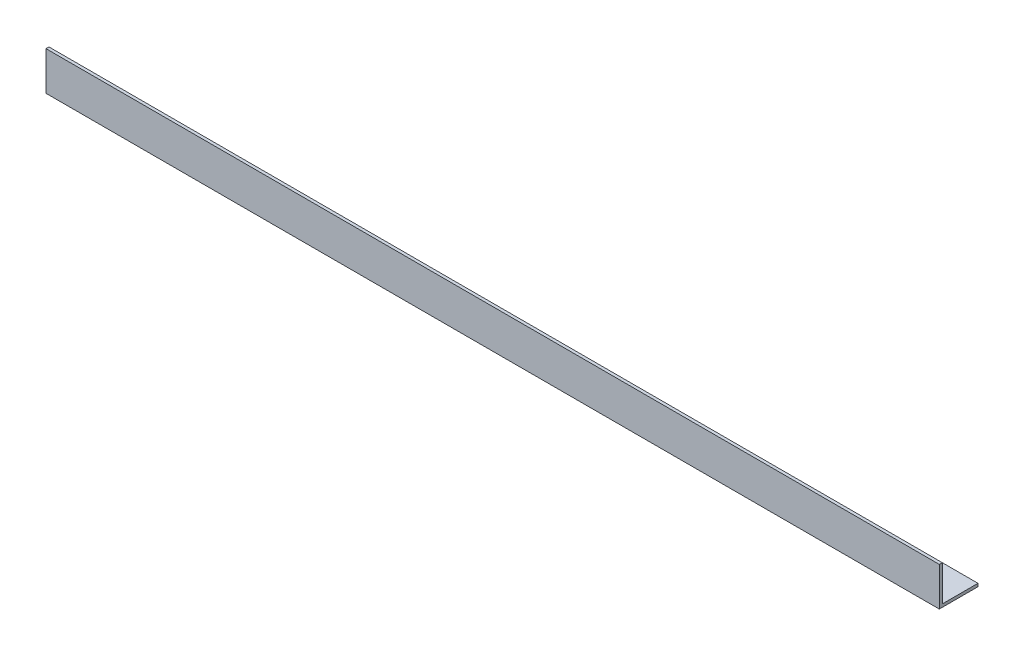
SolidWorks part; units mm, degrees
ref_plane "Спереди" through (0, 0, 0) normal (0, 0, 1) x (1, 0, 0)
ref_plane "Сверху" through (0, 0, 0) normal (0, 1, 0) x (1, 0, 0)
ref_plane "Справа" through (0, 0, 0) normal (1, 0, 0) x (0, 0, -1)
sketch "Эскиз1" plane through (0, 0, 0) normal (1, 0, 0) x (0, 0, -1)
  line L0 (0, 0) -> (0, 65)
  line L1 (0, 0) -> (65, 0)
extrude "Вытянуть-Тонкостенный1" add sketch "Эскиз1" along normal blind 1500 thin thin type one direction reverse wall 5
